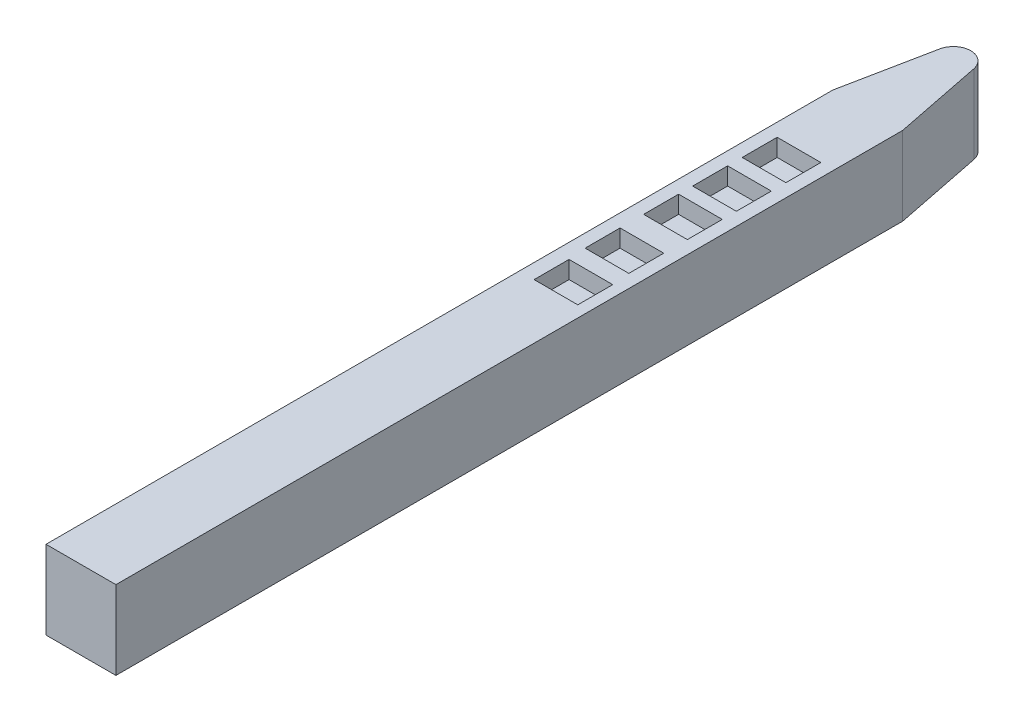
SolidWorks part; units mm, degrees
ref_plane "Front Plane" through (0, 0, 0) normal (0, 0, 1) x (1, 0, 0)
ref_plane "Top Plane" through (0, 0, 0) normal (0, 1, 0) x (1, 0, 0)
ref_plane "Right Plane" through (0, 0, 0) normal (1, 0, 0) x (0, 0, -1)
sketch "Sketch1" plane through (0, 0, 0) normal (0, 1, 0) x (1, 0, 0)
  line L0 (0, 0) -> (0, 1143.3615)
  line L1 (0, 0) -> (101.6, 0)
  line L2 (101.6, 0) -> (101.6, 1143.3615)
  line L3 (0, 1143.3615) -> (50.8, 1397)
  line L4 (50.8, 1397) -> (101.6, 1143.3615)
  line L5 (50.8, 0) -> (50.8, 1705.5122) construction
  dimension "D1" = 1397
  dimension "D2" = 101.6
extrude "Boss-Extrude1" add sketch "Sketch1" along normal blind 114.3
fillet "Fillet2" radius 25.4 1 edges at (50.8, 57.15, -1397)
sketch "Sketch2" plane through (0, 114.3, 0) normal (0, 1, 0) x (1, 0, 0)
  line L0 (50.8, 0) -> (50.8, 1195.0883) construction
  line L1 (0, 0) -> (101.6, 0) construction
  line L2 (19.05, 971.4743) -> (82.55, 971.4743)
  line L3 (19.05, 1043.4464) -> (82.55, 1043.4464)
  line L4 (19.05, 1043.4464) -> (19.05, 992.6464)
  line L5 (19.05, 992.6464) -> (82.55, 992.6464)
  line L6 (82.55, 1043.4464) -> (82.55, 992.6464)
  line L7 (19.05, 1043.4464) -> (82.55, 992.6464) construction
  line L8 (19.05, 992.6464) -> (82.55, 1043.4464) construction
  line L9 (19.05, 971.4743) -> (19.05, 920.6743)
  line L10 (19.05, 920.6743) -> (82.55, 920.6743)
  line L11 (82.55, 971.4743) -> (82.55, 920.6743)
  line L12 (19.05, 971.4743) -> (82.55, 920.6743) construction
  line L13 (19.05, 920.6743) -> (82.55, 971.4743) construction
  line L14 (19.05, 900.2229) -> (82.55, 900.2229)
  line L15 (19.05, 900.2229) -> (19.05, 849.4229)
  line L16 (19.05, 849.4229) -> (82.55, 849.4229)
  line L17 (82.55, 900.2229) -> (82.55, 849.4229)
  line L18 (19.05, 900.2229) -> (82.55, 849.4229) construction
  line L19 (19.05, 849.4229) -> (82.55, 900.2229) construction
  line L20 (19.05, 815.181) -> (82.55, 815.181)
  line L21 (19.05, 815.181) -> (19.05, 764.381)
  line L22 (19.05, 764.381) -> (82.55, 764.381)
  line L23 (82.55, 815.181) -> (82.55, 764.381)
  line L24 (19.05, 815.181) -> (82.55, 764.381) construction
  line L25 (19.05, 764.381) -> (82.55, 815.181) construction
  line L26 (21.5561, 738.5331) -> (85.0561, 738.5331)
  line L27 (21.5561, 738.5331) -> (21.5561, 687.7331)
  line L28 (21.5561, 687.7331) -> (85.0561, 687.7331)
  line L29 (85.0561, 738.5331) -> (85.0561, 687.7331)
  line L30 (21.5561, 738.5331) -> (85.0561, 687.7331) construction
  line L31 (21.5561, 687.7331) -> (85.0561, 738.5331) construction
  point P4 (50.8, 1018.0464)
  point P9 (50.8, 946.0743)
  point P14 (50.8, 874.8229)
  point P19 (50.8, 789.781)
  point P24 (0, 0)
  point P25 (0, 0)
  point P26 (0, 0)
  point P27 (0, 0)
  point P28 (50.8, 789.781)
  point P29 (53.3061, 713.1331)
  dimension "D1" = 63.5
  dimension "D2" = 50.8
  dimension "D3" = 63.5
  dimension "D4" = 50.8
  dimension "D5" = 63.5
  dimension "D6" = 50.8
  dimension "D7" = 63.5
  dimension "D8" = 50.8
  dimension "D9" = 63.5
  dimension "D10" = 50.8
extrude "Cut-Extrude1" cut sketch "Sketch2" against normal blind 25.4
